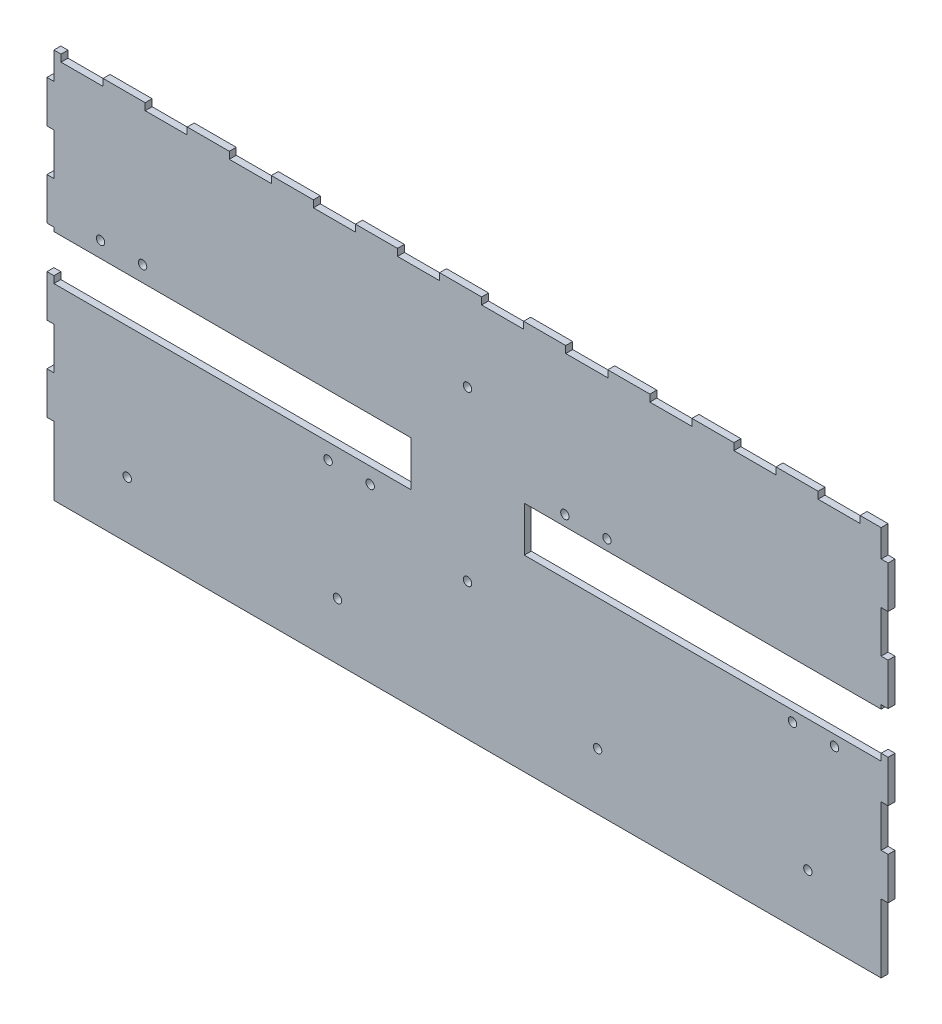
SolidWorks part; units mm, degrees
material "Balsa"
ref_plane "Front Plane" through (0, 0, 0) normal (0, 0, 1) x (1, 0, 0)
ref_plane "Top Plane" through (0, 0, 0) normal (0, 1, 0) x (1, 0, 0)
ref_plane "Right Plane" through (0, 0, 0) normal (1, 0, 0) x (0, 0, -1)
sketch "Sketch1" plane through (0, 0, 0) normal (0, 0, 1) x (1, 0, 0)
  line L0 (227, 160.9919) -> (54, 160.9919) construction
  line L1 (223.7, -24.5) -> (-169.7, -24.5)
  line L2 (223.7, -24.5) -> (223.7, 160.9919)
  line L3 (223.7, 160.9919) -> (-169.7, 160.9919)
  line L4 (-169.7, -24.5) -> (-169.7, 160.9919)
  line L5 (223.7, -24.5) -> (-169.7, 160.9919) construction
  line L6 (223.7, 160.9919) -> (-169.7, -24.5) construction
  line L7 (227, -24.5) -> (223.7, -24.5) construction
  line L10 (223.7, 144.1231) -> (223.7, -24.5) construction
  line L11 (-169.7, -24.5) -> (-169.7, 144.1269) construction
  point P4 (27, 68.246)
extrude "Boss-Extrude1" add sketch "Sketch1" along normal up to surface (3.3 mm away)
sketch "Sketch2" plane through (0, 0, 0) normal (0, 0, -1) x (-1, 0, 0)
  line L0 (-223.7, 160.9919) -> (169.7, 160.9919) construction
  line L1 (0, 0) -> (-54, 0)
  line L2 (0, 0) -> (0, 160.9919)
  line L3 (0, 160.9919) -> (-54, 160.9919)
  line L4 (-54, 0) -> (-54, 160.9919)
  line L5 (0, 0) -> (-54, 160.9919) construction
  line L6 (0, 160.9919) -> (-54, 0) construction
  line L7 (-54, 262.7) -> (-54, 0) construction
  line L8 (-27, 0) -> (-27, 160.9919) construction
  line L9 (169.7, 160.9919) -> (169.7, -24.5) construction
  line L10 (-223.7, 29.5) -> (-54, 29.5)
  line L11 (-223.7, 29.5) -> (-223.7, -24.5)
  line L12 (-223.7, -24.5) -> (-54, -24.5)
  line L13 (-54, 29.5) -> (-54, -24.5)
  line L14 (-223.7, 29.5) -> (-54, -24.5) construction
  line L15 (-223.7, -24.5) -> (-54, 29.5) construction
  line L16 (169.7, 29.5) -> (0, 29.5)
  line L17 (169.7, 29.5) -> (169.7, -24.5)
  line L18 (169.7, -24.5) -> (0, -24.5)
  line L19 (0, 29.5) -> (0, -24.5)
  line L20 (169.7, 29.5) -> (0, -24.5) construction
  line L21 (169.7, -24.5) -> (0, 29.5) construction
  line L22 (-223.7, 2.5) -> (169.7, 2.5) construction
  line L23 (-138.85, -24.5) -> (-138.85, 29.5) construction
  circle A0 centre (-27, 40.496) radius 2
  circle A1 centre (-27, 120.496) radius 2
  circle A2 centre (-188.85, 2.5) radius 2
  circle A3 centre (-88.85, 2.5) radius 2
  circle A4 centre (34.85, 2.5) radius 2
  circle A5 centre (134.85, 2.5) radius 2
  point P4 (-27, 80.496)
  point P20 (-138.85, 2.5)
  point P27 (84.85, 2.5)
  dimension "D1" = 4
  dimension "D2" = 4
  dimension "D3" = 40
  dimension "D4" = 40
  dimension "D5" = 4
  dimension "D6" = 50
extrude "Cut-Extrude1" cut sketch "Sketch2" against normal blind 4 contours A1 | A0 | A2 | A3 | A5 | A4
sketch "Sketch3" plane through (0, 0, 0) normal (0, 0, -1) x (-1, 0, 0)
  line L0 (169.7, 160.9919) -> (169.7, -24.5) construction
  line L1 (169.7, 64.8) -> (-223.7, 64.8)
  line L2 (169.7, 64.8) -> (169.7, 86.2)
  line L3 (169.7, 86.2) -> (-223.7, 86.2)
  line L4 (-223.7, 64.8) -> (-223.7, 86.2)
  line L5 (169.7, 64.8) -> (-223.7, 86.2) construction
  line L6 (169.7, 86.2) -> (-223.7, 64.8) construction
  line L7 (-223.7, -24.5) -> (-223.7, 160.9919) construction
  line L8 (35.8344, 64.8) -> (9.0983, 64.8) construction
  line L9 (142.922, 86.2) -> (163.7817, 86.2) construction
  line L10 (0, 64.8) -> (0, 86.2)
  line L11 (-54, 64.8) -> (-54, 86.2)
  line L12 (-54, 262.7) -> (-54, 0) construction
  line L13 (0, 262.7) -> (0, 0) construction
  line L14 (0, 262.7) -> (0, 0) construction
  point P4 (-27, 75.5)
  line M7 (-223.7, 160.9919) -> (-223.7, -24.5)
  line M9 (169.7, -24.5) -> (169.7, 160.9919)
extrude "Cut-Extrude2" cut sketch "Sketch3" against normal blind 6 contours L10 L1 L3 M9 | L1 L11 L3 M7 region at (-84.85, 75.5, 0) region at (138.85, 75.5, 0)
sketch "Sketch4" plane through (0, 0, 3.3) normal (0, 0, 1) x (1, 0, 0)
  circle A0 centre (93.3034, 91.2) radius 2
  circle A1 centre (73.3034, 91.2) radius 2
  circle A2 centre (181.5258, 59.8) radius 2
  circle A3 centre (201.5258, 59.8) radius 2
  circle A4 centre (-127.5258, 93.7) radius 2
  circle A5 centre (-147.5258, 93.7) radius 2
  circle A6 centre (-19.3034, 57.3) radius 2
  circle A7 centre (-39.3034, 57.3) radius 2
  circle A8 centre (-39.3034, 57.3) radius 2 construction
  circle A9 centre (-19.3034, 57.3) radius 2 construction
  circle A10 centre (-127.5258, 93.7) radius 2 construction
  circle A11 centre (-147.5258, 93.7) radius 2 construction
  circle A12 centre (181.5258, 59.8) radius 2 construction
  circle A13 centre (93.3034, 91.2) radius 2 construction
  circle A14 centre (73.3034, 91.2) radius 2 construction
  circle A15 centre (201.5258, 59.8) radius 2 construction
extrude "Cut-Extrude3" cut sketch "Sketch4" against normal through all
sketch "Sketch5" plane through (0, 0, 3.3) normal (0, 0, 1) x (1, 0, 0)
  line L0 (223.7, 48.0639) -> (227, 48.0639)
  line L1 (223.7, 8.0639) -> (227, 8.0639)
  line L2 (223.7, 8.0639) -> (223.7, 28.0639)
  line L3 (223.7, 28.0639) -> (227, 28.0639)
  line L4 (227, 8.0639) -> (227, 28.0639)
  line L5 (223.7, 8.0639) -> (227, 28.0639) construction
  line L6 (223.7, 28.0639) -> (227, 8.0639) construction
  line L7 (-169.7, 8.0639) -> (-173, 8.0639)
  line L8 (-169.7, 8.0639) -> (-169.7, 28.0639)
  line L9 (-169.7, 28.0639) -> (-173, 28.0639)
  line L10 (-173, 8.0639) -> (-173, 28.0639)
  line L11 (-169.7, 8.0639) -> (-173, 28.0639) construction
  line L12 (-169.7, 28.0639) -> (-173, 8.0639) construction
  line L13 (223.7, 48.0639) -> (223.7, 68.0639)
  line L14 (223.7, 68.0639) -> (227, 68.0639)
  line L15 (227, 48.0639) -> (227, 68.0639)
  line L16 (-169.7, 48.0639) -> (-173, 48.0639)
  line L17 (-169.7, 48.0639) -> (-169.7, 68.0639)
  line L18 (-169.7, 68.0639) -> (-173, 68.0639)
  line L19 (-173, 48.0639) -> (-173, 68.0639)
  line L20 (223.7, 48.0639) -> (227, 68.0639) construction
  line L21 (223.7, 68.0639) -> (227, 48.0639) construction
  line L22 (-169.7, 48.0639) -> (-173, 68.0639) construction
  line L23 (-169.7, 68.0639) -> (-173, 48.0639) construction
  line L24 (223.7, 88.0639) -> (227, 88.0639)
  line L25 (223.7, 88.0639) -> (223.7, 108.0639)
  line L26 (223.7, 108.0639) -> (227, 108.0639)
  line L27 (227, 88.0639) -> (227, 108.0639)
  line L28 (-169.7, 88.0639) -> (-173, 88.0639)
  line L29 (-169.7, 88.0639) -> (-169.7, 108.0639)
  line L30 (-169.7, 108.0639) -> (-173, 108.0639)
  line L31 (-173, 88.0639) -> (-173, 108.0639)
  line L32 (223.7, 88.0639) -> (227, 108.0639) construction
  line L33 (223.7, 108.0639) -> (227, 88.0639) construction
  line L34 (-169.7, 88.0639) -> (-173, 108.0639) construction
  line L35 (-169.7, 108.0639) -> (-173, 88.0639) construction
  line L36 (223.7, 128.0639) -> (227, 128.0639)
  line L37 (223.7, 128.0639) -> (223.7, 148.0639)
  line L38 (223.7, 148.0639) -> (227, 148.0639)
  line L39 (227, 128.0639) -> (227, 148.0639)
  line L40 (-169.7, 128.0639) -> (-173, 128.0639)
  line L41 (-169.7, 128.0639) -> (-169.7, 148.0639)
  line L42 (-169.7, 148.0639) -> (-173, 148.0639)
  line L43 (-173, 128.0639) -> (-173, 148.0639)
  line L44 (223.7, 128.0639) -> (227, 148.0639) construction
  line L45 (223.7, 148.0639) -> (227, 128.0639) construction
  line L46 (-169.7, 128.0639) -> (-173, 148.0639) construction
  line L47 (-169.7, 148.0639) -> (-173, 128.0639) construction
  point P4 (225.35, 18.0639)
  point P11 (-171.35, 18.0639)
  point P19 (225.35, 58.0639)
  point P24 (-171.35, 58.0639)
  point P29 (225.35, 98.0639)
  point P34 (-171.35, 98.0639)
  point P39 (225.35, 138.0639)
  point P44 (-171.35, 138.0639)
  dimension "D1" = 4
extrude "Boss-Extrude2" add sketch "Sketch5" against normal up to surface (3.3 mm away)
sketch "Sketch6" plane through (0, 0, 3.3) normal (0, 0, 1) x (1, 0, 0)
  line L0 (-169.7, 160.9919) -> (223.7, 160.9919) construction
  line L1 (213.7, 160.9919) -> (193.7, 160.9919)
  line L2 (213.7, 160.9919) -> (213.7, 157.6919)
  line L3 (213.7, 157.6919) -> (193.7, 157.6919)
  line L4 (193.7, 160.9919) -> (193.7, 157.6919)
  line L5 (213.7, 160.9919) -> (193.7, 157.6919) construction
  line L6 (213.7, 157.6919) -> (193.7, 160.9919) construction
  line L7 (223.7, 160.9919) -> (223.7, 148.0639) construction
  line L8 (173.7, 160.9919) -> (153.7, 160.9919)
  line L9 (173.7, 160.9919) -> (173.7, 157.6919)
  line L10 (173.7, 157.6919) -> (153.7, 157.6919)
  line L11 (153.7, 160.9919) -> (153.7, 157.6919)
  line L12 (173.7, 160.9919) -> (153.7, 157.6919) construction
  line L13 (173.7, 157.6919) -> (153.7, 160.9919) construction
  line L14 (133.7, 160.9919) -> (113.7, 160.9919)
  line L15 (133.7, 160.9919) -> (133.7, 157.6919)
  line L16 (133.7, 157.6919) -> (113.7, 157.6919)
  line L17 (113.7, 160.9919) -> (113.7, 157.6919)
  line L18 (133.7, 160.9919) -> (113.7, 157.6919) construction
  line L19 (133.7, 157.6919) -> (113.7, 160.9919) construction
  line L20 (93.7, 160.9919) -> (73.7, 160.9919)
  line L21 (93.7, 160.9919) -> (93.7, 157.6919)
  line L22 (93.7, 157.6919) -> (73.7, 157.6919)
  line L23 (73.7, 160.9919) -> (73.7, 157.6919)
  line L24 (93.7, 160.9919) -> (73.7, 157.6919) construction
  line L25 (93.7, 157.6919) -> (73.7, 160.9919) construction
  line L26 (53.7, 160.9919) -> (33.7, 160.9919)
  line L27 (53.7, 160.9919) -> (53.7, 157.6919)
  line L28 (53.7, 157.6919) -> (33.7, 157.6919)
  line L29 (33.7, 160.9919) -> (33.7, 157.6919)
  line L30 (53.7, 160.9919) -> (33.7, 157.6919) construction
  line L31 (53.7, 157.6919) -> (33.7, 160.9919) construction
  line L32 (13.7, 160.9919) -> (-6.3, 160.9919)
  line L33 (13.7, 160.9919) -> (13.7, 157.6919)
  line L34 (13.7, 157.6919) -> (-6.3, 157.6919)
  line L35 (-6.3, 160.9919) -> (-6.3, 157.6919)
  line L36 (13.7, 160.9919) -> (-6.3, 157.6919) construction
  line L37 (13.7, 157.6919) -> (-6.3, 160.9919) construction
  line L38 (-26.3, 160.9919) -> (-46.3, 160.9919)
  line L39 (-26.3, 160.9919) -> (-26.3, 157.6919)
  line L40 (-26.3, 157.6919) -> (-46.3, 157.6919)
  line L41 (-46.3, 160.9919) -> (-46.3, 157.6919)
  line L42 (-26.3, 160.9919) -> (-46.3, 157.6919) construction
  line L43 (-26.3, 157.6919) -> (-46.3, 160.9919) construction
  line L44 (-66.3, 160.9919) -> (-86.3, 160.9919)
  line L45 (-66.3, 160.9919) -> (-66.3, 157.6919)
  line L46 (-66.3, 157.6919) -> (-86.3, 157.6919)
  line L47 (-86.3, 160.9919) -> (-86.3, 157.6919)
  line L48 (-66.3, 160.9919) -> (-86.3, 157.6919) construction
  line L49 (-66.3, 157.6919) -> (-86.3, 160.9919) construction
  line L50 (-106.3, 160.9919) -> (-126.3, 160.9919)
  line L51 (-106.3, 160.9919) -> (-106.3, 157.6919)
  line L52 (-106.3, 157.6919) -> (-126.3, 157.6919)
  line L53 (-126.3, 160.9919) -> (-126.3, 157.6919)
  line L54 (-106.3, 160.9919) -> (-126.3, 157.6919) construction
  line L55 (-106.3, 157.6919) -> (-126.3, 160.9919) construction
  line L56 (-146.3, 160.9919) -> (-166.3, 160.9919)
  line L57 (-146.3, 160.9919) -> (-146.3, 157.6919)
  line L58 (-146.3, 157.6919) -> (-166.3, 157.6919)
  line L59 (-166.3, 160.9919) -> (-166.3, 157.6919)
  line L60 (-146.3, 160.9919) -> (-166.3, 157.6919) construction
  line L61 (-146.3, 157.6919) -> (-166.3, 160.9919) construction
  point P4 (203.7, 159.3419)
  point P14 (163.7, 159.3419)
  point P19 (123.7, 159.3419)
  point P24 (83.7, 159.3419)
  point P29 (43.7, 159.3419)
  point P34 (3.7, 159.3419)
  point P39 (-36.3, 159.3419)
  point P44 (-76.3, 159.3419)
  point P49 (-116.3, 159.3419)
  point P54 (-156.3, 159.3419)
  dimension "D1" = 20
  dimension "D2" = 10
  dimension "D3" = 3.3
  dimension "D4" = 10
extrude "Cut-Extrude4" cut sketch "Sketch6" against normal blind 3.3
